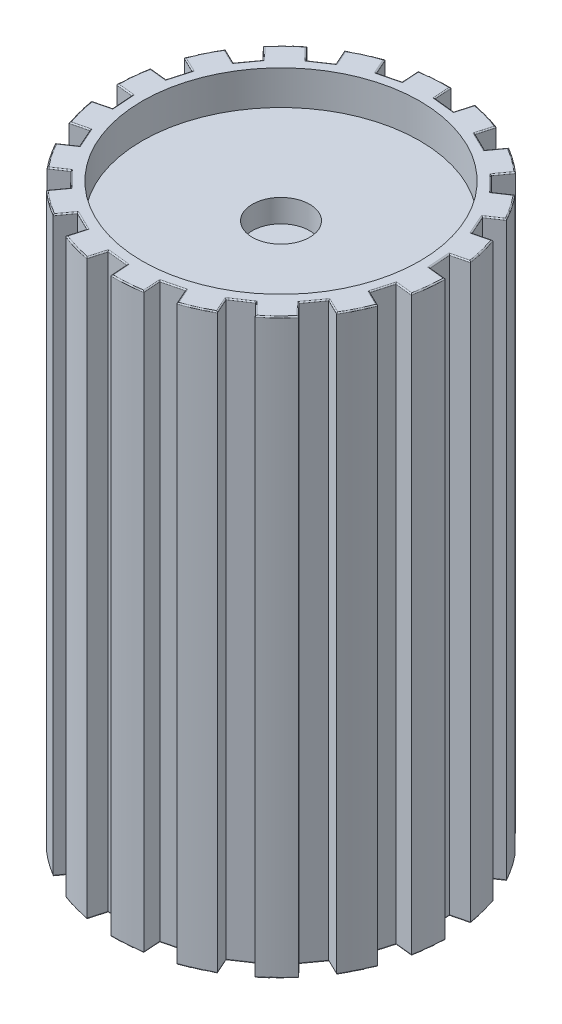
SolidWorks part; units mm, degrees
ref_plane "Front Plane" through (0, 0, 0) normal (0, 0, 1) x (1, 0, 0)
ref_plane "Top Plane" through (0, 0, 0) normal (0, 1, 0) x (1, 0, 0)
ref_plane "Right Plane" through (0, 0, 0) normal (1, 0, 0) x (0, 0, -1)
other "Configuration Table"
sketch "草图1" plane through (0, 0, 0) normal (0, 1, 0) x (1, 0, 0)
  circle A0 centre (0, 0) radius 13
  dimension "D1" = 26
extrude "凸台-拉伸1" add sketch "草图1" along normal blind 50
sketch "草图6" plane through (0, 50, 0) normal (0, 1, 0) x (1, 0, 0)
  circle A0 centre (0, 0) radius 14.5
  dimension "D1" = 29
extrude "凸台-拉伸4" add sketch "草图6" against normal through all
sketch "草图2" plane through (0, 50, 0) normal (0, 1, 0) x (1, 0, 0)
  circle A0 centre (0, 0) radius 12
  dimension "D1" = 24
extrude "切除-拉伸1" cut sketch "草图2" against normal blind 3
sketch "草图7" plane through (0, 50, 0) normal (0, 1, 0) x (1, 0, 0)
  line L0 (-14.206, 5.4386) -> (-12.2092, 4.4648)
  line L1 (-14.206, 5.4386) -> (-14.9294, 2.9159)
  line L2 (-12.2092, 4.4648) -> (-12.72, 2.6836)
  line L3 (-14.9294, 2.9159) -> (-12.72, 2.6836)
  line L4 (-15.2094, 0.2519) -> (-13, 0.0197)
  line L5 (-15.2094, 0.2519) -> (-15.0263, -2.3661)
  line L6 (-15.0263, -2.3661) -> (-12.8707, -1.8287)
  line L7 (-13, 0.0197) -> (-12.8707, -1.8287)
  line L8 (-14.3783, -4.9652) -> (-12.2227, -4.4277)
  line L9 (-14.3783, -4.9652) -> (-13.3108, -7.3627)
  line L10 (-13.3108, -7.3627) -> (-11.4691, -6.1205)
  line L11 (-12.2227, -4.4277) -> (-11.4691, -6.1205)
  line L12 (-11.813, -9.5834) -> (-9.9712, -8.3411)
  line L13 (-11.813, -9.5834) -> (-9.9899, -11.4713)
  line L14 (-9.9899, -11.4713) -> (-8.6841, -9.674)
  line L15 (-9.9712, -8.3411) -> (-8.6841, -9.674)
  line L16 (-7.8229, -13.0457) -> (-6.5171, -11.2485)
  line L17 (-7.8229, -13.0457) -> (-5.464, -14.1962)
  line L18 (-5.464, -14.1962) -> (-4.8517, -12.0607)
  line L19 (-6.5171, -11.2485) -> (-4.8517, -12.0607)
  line L20 (-2.8892, -14.9345) -> (-2.2768, -12.7991)
  line L21 (-2.8892, -14.9345) -> (-0.2791, -15.2089)
  line L22 (-0.2791, -15.2089) -> (-0.4341, -12.9928)
  line L23 (-2.2768, -12.7991) -> (-0.4341, -12.9928)
  line L24 (2.393, -15.022) -> (2.238, -12.8059)
  line L25 (2.393, -15.022) -> (4.9395, -14.3871)
  line L26 (4.9395, -14.3871) -> (4.0359, -12.3577)
  line L27 (2.238, -12.8059) -> (4.0359, -12.3577)
  line L28 (7.3865, -13.2977) -> (6.4829, -11.2682)
  line L29 (7.3865, -13.2977) -> (9.5623, -11.8301)
  line L30 (9.5623, -11.8301) -> (8.0191, -10.232)
  line L31 (6.4829, -11.2682) -> (8.0191, -10.232)
  line L32 (11.4891, -9.9694) -> (9.9459, -8.3713)
  line L33 (11.4891, -9.9694) -> (13.0317, -7.8462)
  line L34 (13.0317, -7.8462) -> (11.035, -6.8723)
  line L35 (9.9459, -8.3713) -> (11.035, -6.8723)
  line L36 (14.206, -5.4386) -> (12.2092, -4.4648)
  line L37 (14.206, -5.4386) -> (14.9294, -2.9159)
  line L38 (14.9294, -2.9159) -> (12.72, -2.6836)
  line L39 (12.2092, -4.4648) -> (12.72, -2.6836)
  line L40 (15.2094, -0.2519) -> (13, -0.0197)
  line L41 (15.2094, -0.2519) -> (15.0263, 2.3661)
  line L42 (15.0263, 2.3661) -> (12.8707, 1.8287)
  line L43 (13, -0.0197) -> (12.8707, 1.8287)
  line L44 (14.3783, 4.9652) -> (12.2227, 4.4277)
  line L45 (14.3783, 4.9652) -> (13.3108, 7.3627)
  line L46 (13.3108, 7.3627) -> (11.4691, 6.1205)
  line L47 (12.2227, 4.4277) -> (11.4691, 6.1205)
  line L48 (11.813, 9.5834) -> (9.9712, 8.3411)
  line L49 (11.813, 9.5834) -> (9.9899, 11.4713)
  line L50 (9.9899, 11.4713) -> (8.6841, 9.674)
  line L51 (9.9712, 8.3411) -> (8.6841, 9.674)
  line L52 (7.8229, 13.0457) -> (6.5171, 11.2485)
  line L53 (7.8229, 13.0457) -> (5.464, 14.1962)
  line L54 (5.464, 14.1962) -> (4.8517, 12.0607)
  line L55 (6.5171, 11.2485) -> (4.8517, 12.0607)
  line L56 (2.8892, 14.9345) -> (2.2768, 12.7991)
  line L57 (2.8892, 14.9345) -> (0.2791, 15.2089)
  line L58 (0.2791, 15.2089) -> (0.4341, 12.9928)
  line L59 (2.2768, 12.7991) -> (0.4341, 12.9928)
  line L60 (-2.393, 15.022) -> (-2.238, 12.8059)
  line L61 (-2.393, 15.022) -> (-4.9395, 14.3871)
  line L62 (-4.9395, 14.3871) -> (-4.0359, 12.3577)
  line L63 (-2.238, 12.8059) -> (-4.0359, 12.3577)
  line L64 (-7.3865, 13.2977) -> (-6.4829, 11.2682)
  line L65 (-7.3865, 13.2977) -> (-9.5623, 11.8301)
  line L66 (-9.5623, 11.8301) -> (-8.0191, 10.232)
  line L67 (-6.4829, 11.2682) -> (-8.0191, 10.232)
  line L68 (-11.4891, 9.9694) -> (-9.9459, 8.3713)
  line L69 (-11.4891, 9.9694) -> (-13.0317, 7.8462)
  line L70 (-13.0317, 7.8462) -> (-11.035, 6.8723)
  line L71 (-9.9459, 8.3713) -> (-11.035, 6.8723)
  circle A0 centre (0, 0) radius 13 construction
  point P78 (0, 0)
  point P150 (0, 0)
  dimension "D1" = 26
  dimension "D2" = 100
  dimension "D3" = 100
  dimension "D4" = 18
extrude "切除-拉伸2" cut sketch "草图7" against normal through all
sketch "草图8" plane through (0, 47, 0) normal (0, 1, 0) x (1, 0, 0)
  circle A0 centre (0, 0) radius 2.5
  dimension "D1" = 5
extrude "切除-拉伸3" cut sketch "草图8" against normal blind 2
fillet "圆角6" radius 0.1 72 edges at (-13.4695, 0, -2.7624) (-12.4646, 0, -3.5742) (-12.8866, 0, -4.7951) (-8.5426, 0, -10.7741) (-10.0725, 0, -10.4305) (-10.4694, 0, -8.9134) (-10.4905, 0, -7.6218) (-11.7123, 0, -7.2026) (-13.0325, 0, -6.3564) (-14.4206, 0, -1.5157) (-13.7495, 0, -0.0985) (-12.9354, 0, 0.9045) (-13.6019, 0, 2.011) (-14.0693, 0, 3.5078) (-12.9539, 0, 4.61) (-11.8459, 0, 5.2741) (-12.0938, 0, 6.5419) (-12.0211, 0, 8.1083) (-10.596, 0, 8.7625) (-9.3277, 0, 9.0076) (-9.127, 0, 10.2837) (-8.5229, 0, 11.7307) (-6.96, 0, 11.8581) (-5.6844, 0, 11.6546) (-5.0594, 0, 12.7851) (-3.9968, 0, 13.9383) (-2.4846, 0, 13.5235) (-1.3555, 0, 12.8959) (-0.3815, 0, 13.7445) (1.0114, 0, 14.4647) (2.2906, 0, 13.5577) (3.137, 0, 12.5818) (4.3424, 0, 13.0461) (5.8976, 0, 13.2464) (6.7894, 0, 11.9566) (7.251, 0, 10.7501) (8.5426, 0, 10.7741) (10.0725, 0, 10.4305) (10.4694, 0, 8.9134) (10.4905, 0, 7.6218) (11.7123, 0, 7.2026) (13.0325, 0, 6.3564) (12.8866, 0, 4.7951) (12.4646, 0, 3.5742) (13.4695, 0, 2.7624) (14.4206, 0, 1.5157) (13.7495, 0, 0.0985) (12.9354, 0, -0.9045) (13.6019, 0, -2.011) (14.0693, 0, -3.5078) (12.9539, 0, -4.61) (11.8459, 0, -5.2741) (12.0938, 0, -6.5419) (12.0211, 0, -8.1083) (10.596, 0, -8.7625) (9.3277, 0, -9.0076) (9.127, 0, -10.2837) (8.5229, 0, -11.7307) (6.96, 0, -11.8581) (5.6844, 0, -11.6546) (5.0594, 0, -12.7851) (3.9968, 0, -13.9383) (2.4846, 0, -13.5235) (1.3555, 0, -12.8959) (0.3815, 0, -13.7445) (-1.0114, 0, -14.4647) (-2.2906, 0, -13.5577) (-3.137, 0, -12.5818) (-4.3424, 0, -13.0461) (-5.8976, 0, -13.2464) (-6.7894, 0, -11.9566) (-7.251, 0, -10.7501)
fillet "圆角7" radius 0.1 73 edges at (0, 50, 12) (-12.8866, 50, -4.7951) (-12.4646, 50, -3.5742) (-13.4695, 50, -2.7624) (-5.8976, 50, -13.2464) (-4.3424, 50, -13.0461) (-3.137, 50, -12.5818) (-2.2906, 50, -13.5577) (-1.0114, 50, -14.4647) (0.3815, 50, -13.7445) (1.3555, 50, -12.8959) (2.4846, 50, -13.5235) (3.9968, 50, -13.9383) (5.0594, 50, -12.7851) (5.6844, 50, -11.6546) (6.96, 50, -11.8581) (8.5229, 50, -11.7307) (9.127, 50, -10.2837) (9.3277, 50, -9.0076) (10.596, 50, -8.7625) (12.0211, 50, -8.1083) (12.0938, 50, -6.5419) (11.8459, 50, -5.2741) (12.9539, 50, -4.61) (14.0693, 50, -3.5078) (13.6019, 50, -2.011) (12.9354, 50, -0.9045) (13.7495, 50, 0.0985) (14.4206, 50, 1.5157) (13.4695, 50, 2.7624) (12.4646, 50, 3.5742) (12.8866, 50, 4.7951) (13.0325, 50, 6.3564) (11.7123, 50, 7.2026) (10.4905, 50, 7.6218) (10.4694, 50, 8.9134) (10.0725, 50, 10.4305) (8.5426, 50, 10.7741) (7.251, 50, 10.7501) (6.7894, 50, 11.9566) (5.8976, 50, 13.2464) (4.3424, 50, 13.0461) (3.137, 50, 12.5818) (2.2906, 50, 13.5577) (1.0114, 50, 14.4647) (-0.3815, 50, 13.7445) (-1.3555, 50, 12.8959) (-2.4846, 50, 13.5235) (-3.9968, 50, 13.9383) (-5.0594, 50, 12.7851) (-5.6844, 50, 11.6546) (-6.96, 50, 11.8581) (-8.5229, 50, 11.7307) (-9.127, 50, 10.2837) (-9.3277, 50, 9.0076) (-10.596, 50, 8.7625) (-12.0211, 50, 8.1083) (-12.0938, 50, 6.5419) (-11.8459, 50, 5.2741) (-12.9539, 50, 4.61) (-14.0693, 50, 3.5078) (-13.6019, 50, 2.011) (-12.9354, 50, 0.9045) (-13.7495, 50, -0.0985) (-14.4206, 50, -1.5157) (-13.0325, 50, -6.3564) (-11.7123, 50, -7.2026) (-10.4905, 50, -7.6218) (-10.4694, 50, -8.9134) (-10.0725, 50, -10.4305) (-8.5426, 50, -10.7741) (-7.251, 50, -10.7501) (-6.7894, 50, -11.9566)
sketch "草图9" plane through (0, 47, 0) normal (0, 1, 0) x (1, 0, 0)
  circle A0 centre (0, 0) radius 12.1
  circle A1 centre (0, 0) radius 12 construction
  dimension "D1" = 0.1
extrude "切除-拉伸4" cut sketch "草图9" along normal through all
